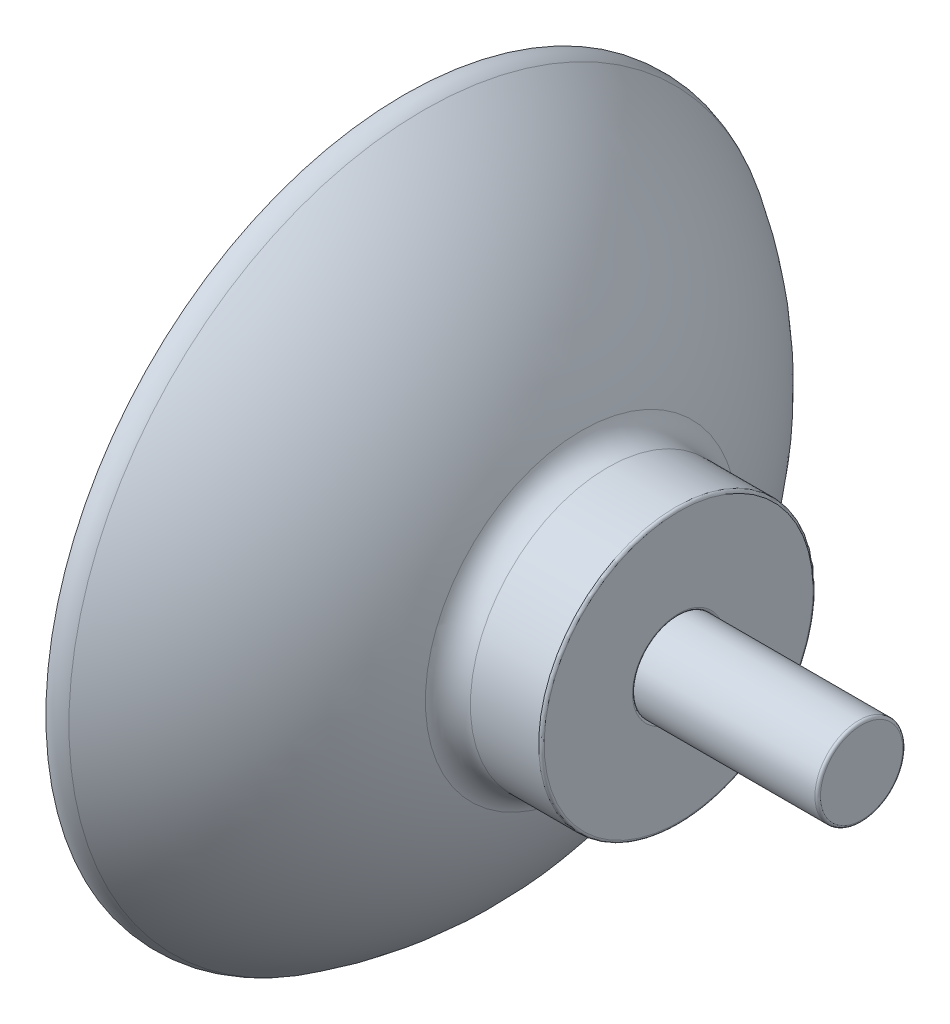
SolidWorks part; units mm, degrees
ref_plane "Front Plane" through (0, 0, 0) normal (0, 0, 1) x (1, 0, 0)
ref_plane "Top Plane" through (0, 0, 0) normal (0, 1, 0) x (1, 0, 0)
ref_plane "Right Plane" through (0, 0, 0) normal (1, 0, 0) x (0, 0, -1)
sketch "Sketch1" plane through (0, 0, 0) normal (0, 0, 1) x (1, 0, 0)
  line L0 (0, 0) -> (-10, 0) construction
  line L1 (0, 0) -> (5, 0) construction
  line L2 (0, 0) -> (0, 7.5)
  line L3 (0, 7.5) -> (5, 7.5)
  line L4 (5, 0) -> (5, 7.5)
  line L5 (2, 0) -> (4, 0) construction
  line L6 (2, 0) -> (2, 4.75)
  line L7 (2, 4.75) -> (4, 4.75)
  line L8 (4, 0) -> (4, 4.75)
  line L9 (-10, 0) -> (-10, 20) construction
  line L10 (-10, 20) -> (-10, 19.5)
  line L11 (5, 0) -> (4, 0)
  line L12 (2, 0) -> (0, 0)
  line L13 (4, 2.375) -> (5, 2.375)
  arc A0 (0, 7.5) -> (-10, 20) centre (-19.3122, 2.3002) ccw
  arc A1 (-10, 19.5) -> (0, 4) centre (-21.7836, 0.9219) cw
  dimension "D8" = 20
  dimension "D11" = 22
  dimension "D1" = 7.5
  dimension "D2" = 5
  dimension "D3" = 4.75
  dimension "D4" = 2
  dimension "D5" = 1
  dimension "D6" = 20
  dimension "D7" = 10
  dimension "D9" = 0.5
  dimension "D10" = 3.5
revolve "Revolve1" add sketch "Sketch1" angle 360 about L0 region at (0.0901, 2, 0) region at (-3.1385, 12.951, 0)
fillet "Fillet2" radius 0.15 5 edges at (4, 2.375, 0) (5, 2.375, 0) (5, 7.5, 0) (-10, 19.5, 0) (0, 4, 0)
fillet "Fillet3" radius 1.5 2 edges at (0, 7.5, 0) (-10, 20, 0)
sketch "Sketch2" plane through (0, 0, 0) normal (0, 0, 1) x (1, 0, 0)
  line L0 (2, 0) -> (2, 4.75)
  line L1 (2, -4.75) -> (2, 4.75) construction
  line L2 (2, 4.75) -> (4, 4.75)
  line L3 (4, 4.75) -> (4, -4.75) construction
  line L4 (4, 4.75) -> (4, 2.4)
  line L5 (4, 2.4) -> (15, 2.4)
  line L6 (15, 2.4) -> (15, 0)
  line L7 (2, 0) -> (4, 0) construction
  line L8 (15, 0) -> (2, 0)
  line L9 (5, -7.35) -> (5, 7.35) construction
  dimension "D1" = 10
  dimension "D2" = 2.35
revolve "Revolve2" add sketch "Sketch2" angle 360 about L8
fillet "Fillet4" radius 0.15 1 edges at (15, 2.4, 0)
